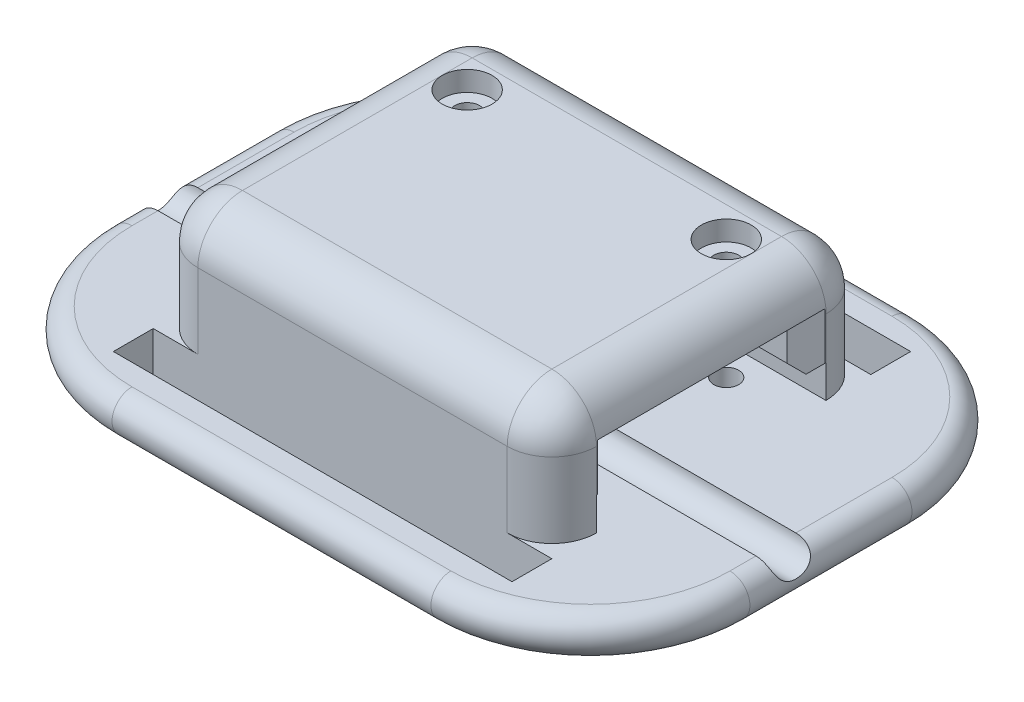
SolidWorks part; units mm, degrees
ref_plane "Front Plane" through (0, 0, 0) normal (0, 0, 1) x (1, 0, 0)
ref_plane "Top Plane" through (0, 0, 0) normal (0, 1, 0) x (1, 0, 0)
ref_plane "Right Plane" through (0, 0, 0) normal (1, 0, 0) x (0, 0, -1)
sketch "Sketch1" plane through (0, 0, 0) normal (0, 1, 0) x (1, 0, 0)
  line L1 (-7.9604, 16.7072) -> (23.7896, 16.7072)
  line L2 (-7.9604, 16.7072) -> (-7.9604, -8.6928)
  line L3 (-7.9604, -8.6928) -> (23.7896, -8.6928)
  line L4 (23.7896, 16.7072) -> (23.7896, -8.6928)
  dimension "D1" = 31.75
  dimension "D2" = 25.4
extrude "Boss-Extrude1" add sketch "Sketch1" along normal blind 12.7
sketch "Sketch2" plane through (23.7896, 0, 0) normal (1, 0, 0) x (0, 0, -1)
  line L0 (-8.6928, 12.7) -> (16.7072, 0) construction
  line L1 (16.7072, 12.7) -> (-8.6928, 0) construction
  line L3 (-5.1209, 3.175) -> (13.1353, 3.175)
  line L4 (-5.1209, 3.175) -> (-5.1209, 9.525)
  line L5 (-5.1209, 9.525) -> (13.1353, 9.525)
  line L6 (13.1353, 3.175) -> (13.1353, 9.525)
  line L7 (-5.1209, 3.175) -> (13.1353, 9.525) construction
  line L8 (-5.1209, 9.525) -> (13.1353, 3.175) construction
  point P4 (4.0072, 6.35)
  point P10 (4.0072, 6.35)
  dimension "D1" = 18.2562
  dimension "D2" = 6.35
extrude "Cut-Extrude3" cut sketch "Sketch2" against normal through all
sketch "Sketch4" plane through (23.7896, 0, 0) normal (1, 0, 0) x (0, 0, -1)
  line L0 (-5.1209, 3.175) -> (13.1353, 3.175) construction
  line L1 (-5.1209, 9.525) -> (-3.5334, 9.525)
  line L2 (-5.1209, 9.525) -> (-5.1209, 4.7625)
  line L3 (-5.1209, 4.7625) -> (-3.5334, 4.7625)
  line L4 (-3.5334, 9.525) -> (-3.5334, 4.7625)
  line L5 (4.0072, 9.525) -> (4.0072, 3.175) construction
  line L6 (13.1353, 4.7625) -> (11.5478, 4.7625)
  line L7 (11.5478, 9.525) -> (11.5478, 4.7625)
  line L8 (13.1353, 9.525) -> (11.5478, 9.525)
  line L9 (13.1353, 9.525) -> (13.1353, 4.7625)
  dimension "D1" = 1.5875
  dimension "D2" = 1.5875
extrude "Boss-Extrude2" add sketch "Sketch4" against normal through all
sketch "Sketch5" plane through (0, 3.175, 0) normal (0, 1, 0) x (1, 0, 0)
  line L0 (-4.7854, 13.1353) -> (-2.4042, 13.1353) construction
  line L1 (-4.7854, -5.1209) -> (20.6146, -5.1209) construction
  line L2 (-4.7854, -5.1209) -> (-4.7854, 13.1353) construction
  line L8 (-4.7854, 13.1353) -> (20.6146, 13.1353) construction
  line L9 (20.6146, -5.1209) -> (20.6146, 13.1353) construction
  line L10 (-4.7854, -5.1209) -> (20.6146, 13.1353) construction
  line L11 (-4.7854, 13.1353) -> (20.6146, -5.1209) construction
  line L12 (-2.4042, 13.1353) -> (-2.4042, 10.7541) construction
  line L13 (7.9146, 4.0072) -> (7.9146, 5.4175) construction
  circle A0 centre (-2.4042, 10.7541) radius 0.9922
  circle A1 centre (18.2333, 10.7541) radius 0.9922
  point P0 (7.9146, 4.0072)
  point P1 (7.9146, 4.0072)
  point P6 (7.9146, 4.0072)
  dimension "D1" = 25.4
  dimension "D2" = 18.2562
extrude "Cut-Extrude5" cut sketch "Sketch5" against normal through all and the other way through all
sketch "Sketch6" plane through (0, 0, 0) normal (0, -1, 0) x (1, 0, 0)
  line L1 (-0.0229, -10.7541) -> (-1.2136, -8.6919)
  line L2 (-1.2136, -8.6919) -> (-3.5948, -8.6919)
  line L3 (-3.5948, -8.6919) -> (-4.7854, -10.7541)
  line L4 (-4.7854, -10.7541) -> (-3.5948, -12.8163)
  line L5 (-3.5948, -12.8163) -> (-1.2136, -12.8163)
  line L6 (-1.2136, -12.8163) -> (-0.0229, -10.7541)
  line L7 (20.6146, -10.7541) -> (19.4239, -8.6919)
  line L8 (19.4239, -8.6919) -> (17.0427, -8.6919)
  line L9 (17.0427, -8.6919) -> (15.8521, -10.7541)
  line L10 (15.8521, -10.7541) -> (17.0427, -12.8163)
  line L11 (17.0427, -12.8163) -> (19.4239, -12.8163)
  line L12 (19.4239, -12.8163) -> (20.6146, -10.7541)
  circle A0 centre (-2.4042, -10.7541) radius 2.3813 construction
  circle A1 centre (18.2333, -10.7541) radius 2.3813 construction
extrude "Cut-Extrude6" cut sketch "Sketch6" against normal blind 1.5875
sketch "Sketch7" plane through (0, 12.7, 0) normal (0, 1, 0) x (1, 0, 0)
  circle A0 centre (-2.4042, 10.7541) radius 1.9844
  circle A1 centre (18.2333, 10.7541) radius 1.9844
extrude "Cut-Extrude7" cut sketch "Sketch7" against normal blind 1.5875
sketch "Sketch8" plane through (0, 0, 0) normal (0, -1, 0) x (1, 0, 0)
  line L1 (-17.4854, -23.1602) -> (33.3146, -23.1602)
  line L2 (-17.4854, -23.1602) -> (-17.4854, 15.1457)
  line L3 (-17.4854, 15.1457) -> (33.3146, 15.1457)
  line L4 (33.3146, -23.1602) -> (33.3146, 15.1457)
  line L5 (-17.4854, -23.1602) -> (33.3146, 15.1457) construction
  line L6 (-17.4854, 15.1457) -> (33.3146, -23.1602) construction
  line L7 (-7.9604, 8.6928) -> (23.7896, 8.6928)
  line L8 (-7.9604, 8.6928) -> (-7.9604, -16.7072)
  line L9 (-7.9604, -16.7072) -> (23.7896, -16.7072)
  line L10 (23.7896, 8.6928) -> (23.7896, -16.7072)
  point P0 (7.9146, -4.0072)
  point P10 (7.9146, -4.0072)
extrude "Boss-Extrude3" add sketch "Sketch8" against normal up to surface (3.175 mm away) contours L8 L7 L10 L9 | L2 L1 L4 L3 up to face at (-2.4042, 3.175, -11.7463)
sketch "Sketch10" plane through (0, 3.175, 0) normal (0, 1, 0) x (1, 0, 0)
  line L0 (-7.9604, 4.0072) -> (23.7896, 4.0072) construction
  line L1 (-7.9604, 16.7072) -> (23.7896, 16.7072)
  line L2 (-7.9604, 16.7072) -> (-7.9604, 19.8822)
  line L3 (-7.9604, 19.8822) -> (23.7896, 19.8822)
  line L4 (23.7896, 16.7072) -> (23.7896, 19.8822)
  line L5 (-7.9604, -11.8678) -> (23.7896, -11.8678)
  line L6 (23.7896, -8.6928) -> (23.7896, -11.8678)
  line L7 (-7.9604, -8.6928) -> (23.7896, -8.6928)
  line L8 (-7.9604, -8.6928) -> (-7.9604, -11.8678)
  dimension "D1" = 3.175
extrude "Cut-Extrude8" cut sketch "Sketch10" against normal through all
fillet "Fillet6" radius 12.7 4 edges at (-17.4854, 1.5875, 15.1457) (-17.4854, 1.5875, -23.1602) (33.3146, 1.5875, -23.1602) (33.3146, 1.5875, 15.1457)
chamfer "Chamfer1" distance 1.016 angle 45 6 edges at (-5.48, 4.7625, -11.5478) (-7.9604, 4.7625, -12.3416) (-7.9604, 4.7625, 4.3272) (7.9146, 4.7625, 3.5334) (23.7896, 4.7625, 4.3272) (23.7896, 4.7625, -12.3416)
chamfer "Chamfer2" distance 1.524 angle 45 4 edges at (-7.9604, 7.6518, -11.5478) (-7.9604, 7.6517, 3.5334) (23.7896, 7.6517, 3.5334) (23.7896, 7.6518, -11.5478)
fillet "Fillet7" radius 3.556 8 edges at (7.9146, 12.7, 8.6928) (23.7896, 7.9375, 8.6928) (23.7896, 12.7, -4.0072) (23.7896, 7.9375, -16.7072) (-7.9604, 12.7, -4.0072) (7.9146, 12.7, -16.7072) (-7.9604, 7.9375, 8.6928) (-7.9604, 7.9375, -16.7072)
fillet "Fillet10" 2 edges at (-13.7657, 0, 11.426) (-13.7657, 3.175, 11.426) type full round first side face at (7.9146, 0, -18.2947) second side face at (7.9146, 3.175, -16.0639) middle face at (-12.4506, 1.5875, 10.1109)
sketch3d "3DSketch1" plane through (0, 0, 0) normal (0, 0, 1) x (1, 0, 0)
  dimension "D1" = 50.8
sketch "Sketch13" plane through (50.8, 0, 0) normal (1, 0, 0) x (0, 0, -1)
  line L0 (-5.1368, 9.144) -> (-5.1368, 3.175) construction
  line L1 (-5.1368, 9.144) -> (-5.1368, 3.175)
  line L2 (-5.1368, 3.175) -> (1.2132, 3.175)
  circle A0 centre (1.2132, 3.175) radius 1.5875
  dimension "D1" = 6.35
extrude "Cut-Extrude9" cut sketch "Sketch13" against normal through all contours A0
sketch "Sketch14" plane through (0, 3.175, 0) normal (0, 1, 0) x (1, 0, 0)
  line L0 (-9.7117, -5.1209) -> (-9.7117, 13.1353)
  line L1 (25.164, -5.1209) -> (25.164, 13.1353)
  text T0 "<b>SQUAT</b>"
